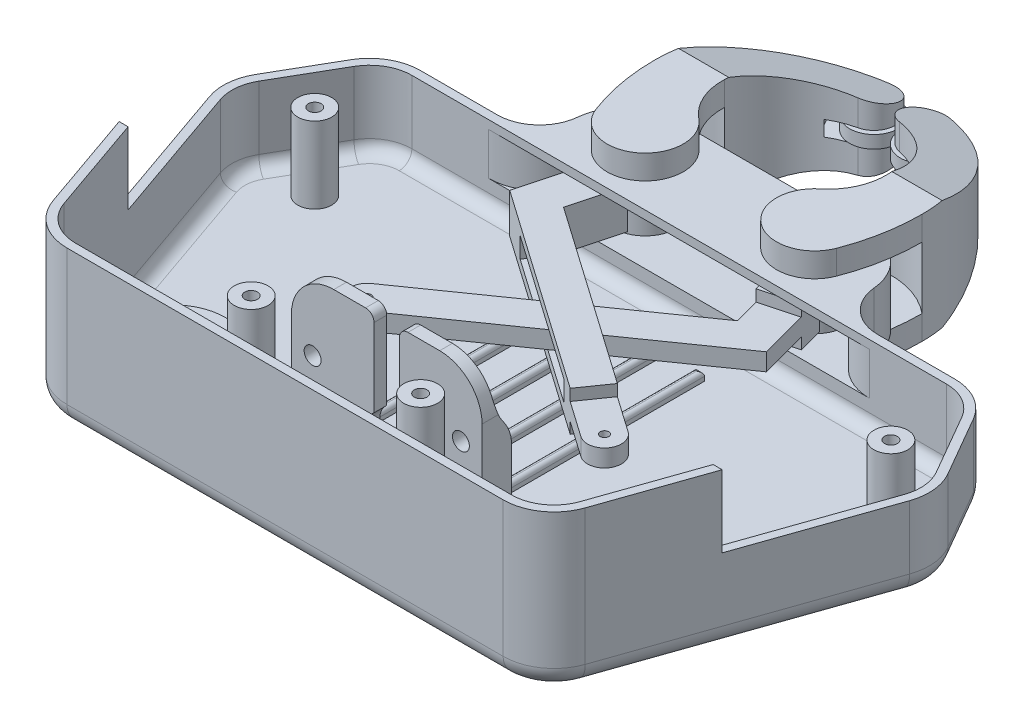
SolidWorks part; units mm, degrees
ref_plane "Front Plane" through (0, 0, 0) normal (0, 0, 1) x (1, 0, 0)
ref_plane "Top Plane" through (0, 0, 0) normal (0, 1, 0) x (1, 0, 0)
ref_plane "Right Plane" through (0, 0, 0) normal (1, 0, 0) x (0, 0, -1)
sketch "Sketch1" plane through (0, 0, 0) normal (0, 1, 0) x (1, 0, 0)
  line L0 (-70, -55) -> (-35, -55)
  line L1 (70, -55) -> (84.4338, -80)
  line L2 (84.4338, -80) -> (60, -150)
  line L3 (60, -150) -> (-60, -150)
  line L4 (-60, -150) -> (-84.4338, -80)
  line L5 (-84.4338, -80) -> (-70, -55)
  line L6 (-35, -55) -> (-35, -35)
  line L7 (-35, -35) -> (35, -35)
  line L8 (35, -35) -> (35, -55)
  line L9 (0, -55) -> (0, -122.8119) construction
  line L10 (35, -55) -> (70, -55)
  point P15 (0, -150)
  dimension "D1" = 25
  dimension "D2" = 140
  dimension "D3" = 70
  dimension "D4" = 120
  dimension "D5" = 70
  dimension "D6" = 55
  dimension "D7" = 120
  dimension "D8" = 20
  dimension "D9" = 70
  dimension "D10" = 35
extrude "Boss-Extrude1" add sketch "Sketch1" along normal blind 2
sketch "Sketch2" plane through (0, 2, 0) normal (0, 1, 0) x (1, 0, 0)
  line L0 (84.4338, -80) -> (70, -55) construction
  line L1 (60, -150) -> (84.4338, -80) construction
  line L2 (-60, -150) -> (60, -150) construction
  line L3 (-84.4338, -80) -> (-60, -150) construction
  line L4 (-70, -55) -> (-84.4338, -80) construction
  line L6 (84.4338, -80) -> (70, -55)
  line L7 (60, -150) -> (84.4338, -80)
  line L8 (-60, -150) -> (60, -150)
  line L9 (-84.4338, -80) -> (-60, -150)
  line L10 (-70, -55) -> (-84.4338, -80)
  line L11 (70, -55) -> (35, -55)
  line L12 (68.8453, -57) -> (33, -57)
  line L13 (-68.8453, -57) -> (-82.2434, -80.2062)
  line L14 (-82.2434, -80.2062) -> (-58.5798, -148)
  line L15 (-58.5798, -148) -> (58.5798, -148)
  line L16 (58.5798, -148) -> (82.2434, -80.2062)
  line L17 (82.2434, -80.2062) -> (68.8453, -57)
  line L18 (-35, -55) -> (-35, -35)
  line L19 (-35, -35) -> (35, -35)
  line L20 (35, -35) -> (35, -55)
  line L21 (-35, -55) -> (-70, -55)
  line L22 (-33, -57) -> (-33, -37)
  line L23 (70, -55) -> (-70, -55) construction
  line L24 (-33, -37) -> (33, -37)
  line L25 (33, -37) -> (33, -57)
  line L26 (-33, -57) -> (-68.8453, -57)
  line L28 (68.8453, -57) -> (-68.8453, -57) construction
  dimension "D1" = 2
  dimension "D2" = 2
  dimension "D3" = 2
  dimension "D4" = 2
extrude "Boss-Extrude2" add sketch "Sketch2" along normal blind 35
sketch "Sketch20" plane through (0, 0, 0) normal (0, -1, 0) x (1, 0, 0)
  line L0 (70, 55) -> (35, 55) construction
  line L1 (-35, 35) -> (35, 35)
  line L2 (-35, 35) -> (-35, 55)
  line L3 (-35, 55) -> (35, 55)
  line L4 (35, 35) -> (35, 55)
  line L5 (35, 55) -> (35, 35) construction
  line L6 (35, 35) -> (-35, 35) construction
  line L7 (-35, 35) -> (-35, 55) construction
extrude "Cut-Extrude7" cut sketch "Sketch20" against normal blind 8
sketch "Sketch21" plane through (0, 8, 0) normal (0, -1, 0) x (1, 0, 0)
  line L1 (-35, 35) -> (35, 35)
  line L2 (-35, 35) -> (-35, 55)
  line L3 (-35, 55) -> (35, 55)
  line L4 (35, 35) -> (35, 55)
extrude "Boss-Extrude12" add sketch "Sketch21" along normal blind 2
sketch "Sketch22" plane through (0, 0, 55) normal (0, 0, 1) x (1, 0, 0)
  line L1 (-33, 2) -> (33, 2)
  line L2 (-33, 2) -> (-33, 8)
  line L3 (-33, 8) -> (33, 8)
  line L4 (33, 2) -> (33, 8)
extrude "Boss-Extrude13" add sketch "Sketch22" along normal blind 2
sketch "Sketch23" plane through (0, 37, 0) normal (0, 1, 0) x (1, 0, 0)
  line L0 (35, -35) -> (-35, -35) construction
  line L1 (-35, -57) -> (35, -57)
  line L2 (-35, -57) -> (-35, -35)
  line L3 (-35, -35) -> (35, -35)
  line L4 (35, -57) -> (35, -35)
  line L5 (-35, -35) -> (-35, -55) construction
  line L6 (35, -55) -> (35, -35) construction
  line L7 (33, -57) -> (-33, -57) construction
extrude "Cut-Extrude8" cut sketch "Sketch23" against normal offset from surface (19 mm away) 12 up to face at (0, 6, 45)
sketch "Sketch24" plane through (0, 18, 0) normal (0, 1, 0) x (1, 0, 0)
  line L1 (-35, -35) -> (35, -35)
  line L2 (-35, -35) -> (-35, -57)
  line L3 (-35, -57) -> (35, -57)
  line L4 (35, -35) -> (35, -57)
  line L5 (-35, -35) -> (35, -35) construction
  line L6 (-35, -55) -> (-35, -35) construction
  line L8 (35, -35) -> (35, -55) construction
  line L9 (-35, -57) -> (-68.8453, -57) construction
extrude "Boss-Extrude16" add sketch "Sketch24" along normal blind 2
sketch "Sketch26" plane through (0, 0, 0) normal (0, -1, 0) x (1, 0, 0)
  line L0 (0, 35) -> (0, 168.1743) construction
  line L1 (-35, 35) -> (35, 35) construction
  circle A0 centre (20, 45) radius 7.5
  circle A1 centre (-20, 45) radius 7.5
  dimension "D1" = 15
  dimension "D2" = 10
  dimension "D3" = 20
extrude "Cut-Extrude9" cut sketch "Sketch26" against normal through all
sketch "Sketch27" plane through (0, 8, 0) normal (0, 1, 0) x (1, 0, 0)
  line L0 (-29.5, -45) -> (-27.5, -45)
  line L1 (-10.5, -45) -> (-12.5, -45)
  line L2 (0, -35) -> (0, -72.4721) construction
  line L3 (35, -35) -> (-35, -35) construction
  line L4 (29.5, -45) -> (27.5, -45)
  line L5 (10.5, -45) -> (12.5, -45)
  arc A0 (-27.5, -45) -> (-12.5, -45) centre (-20, -45) cw
  circle A1 centre (-20, -45) radius 7.5 construction
  arc A2 (-10.5, -45) -> (-29.5, -45) centre (-20, -45) ccw
  arc A3 (27.5, -45) -> (12.5, -45) centre (20, -45) ccw
  arc A4 (10.5, -45) -> (29.5, -45) centre (20, -45) cw
  dimension "D1" = 9.5
extrude "Boss-Extrude18" add sketch "Sketch27" along normal up to surface (10 mm away) up to face at (20, 18, 52.5)
sketch "Sketch25" plane through (0, 20, 0) normal (0, 1, 0) x (1, 0, 0)
  line L0 (35, -57) -> (35, -55) construction
  line L1 (-35, -57) -> (35, -57)
  line L2 (-35, -57) -> (-35, -55)
  line L3 (-35, -55) -> (35, -55)
  line L4 (35, -57) -> (35, -55)
  line L5 (-35, -57) -> (35, -57) construction
  line L6 (-35, -55) -> (-35, -57) construction
  line L7 (-35, -55) -> (-70, -55) construction
extrude "Boss-Extrude17" add sketch "Sketch25" along normal up to surface (17 mm away) up to face at (0, 37, 85.2758)
fillet "Fillet8" radius 10 2 edges at (-33, 13, 37) (33, 13, 37)
fillet "Fillet9" radius 12 2 edges at (35, 13, 35) (-35, 13, 35)
sketch "Sketch32" plane through (0, 6, 0) normal (0, -1, 0) x (1, 0, 0)
  circle A0 centre (-20, 45) radius 7.35
  circle A1 centre (-20, 45) radius 7.5 construction
  dimension "D1" = 14.7
extrude "Boss-Extrude22" add sketch "Sketch32" against normal offset from surface (14.6 mm away) 0.3 from offset 0.3 separate body up to face at (0, 20, 44.8382) offset beyond the face yes
ref_plane "Plane6" through (0, 13, 0) normal (0, -1, 0) x (-1, 0, 0)
sketch "Sketch34" plane through (0, 13, 0) normal (0, -1, 0) x (-1, 0, 0)
  line L0 (0, -55) -> (0, -6.1056) construction
  line L1 (-35, -55) -> (35, -55) construction
  circle A0 centre (6, -5) radius 6
  circle A1 centre (20, -45) radius 7.5 construction
  circle A2 centre (20, -45) radius 7.5 construction
  circle A3 centre (6, -5) radius 2.8
  dimension "D1" = 12
  dimension "D3" = 5.6
  dimension "D2" = 40
extrude "Boss-Extrude23" add sketch "Sketch34" along normal mid plane 3 separate body
sketch "Sketch36" plane through (0, 13, 0) normal (0, -1, 0) x (-1, 0, 0)
  circle A0 centre (6, -5) radius 2.5
  dimension "D1" = 5
extrude "Boss-Extrude24" add sketch "Sketch36" along normal mid plane 3.6 separate body
sketch "Sketch37" plane through (0, 11.2, 0) normal (0, -1, 0) x (1, 0, 0)
  line L0 (-1.0405, 27.7489) -> (-20, 45) construction
  line L1 (-6, 5) -> (-1.0405, 27.7489) construction
  line L2 (0.4875, 31.2396) -> (-20, 45) construction
  line L3 (0.4875, 31.2396) -> (-6, 5) construction
  arc A0 (-4.935, 9.8853) -> (-7.2001, 0.1462) centre (-6, 5) cw
  circle A1 centre (-20, 45) radius 7.35 construction
  arc A2 (-14.5636, 40.0535) -> (-26.1015, 49.0981) centre (-20, 45) ccw construction
  arc A3 (-4.935, 9.8853) -> (-14.5636, 40.0535) centre (-1.0405, 27.7489) cw construction
  arc A4 (-26.1015, 49.0981) -> (-7.2001, 0.1462) centre (0.4875, 31.2396) ccw construction
  arc A5 (-31.5421, 31.1877) -> (-19.3089, 27.0133) centre (-20, 45) ccw
  arc A6 (-31.5421, 31.1877) -> (-7.2001, 0.1462) centre (0.4875, 31.2396) ccw
  arc A7 (-19.3089, 27.0133) -> (-4.935, 9.8853) centre (-1.0405, 27.7489) ccw
  dimension "D1" = 5
  dimension "D4" = 18
  dimension "D2" = 60
  dimension "D3" = 70
extrude "Boss-Extrude25" add sketch "Sketch37" along normal up to surface (11.2 mm away) up to face at (0, 0, 95)
sketch "Sketch39" plane through (0, 5.7, 0) normal (0, -1, 0) x (1, 0, 0)
  arc A0 (-14.3353, 38.0064) -> (-28.4038, 48.2211) centre (-20, 45) ccw
  arc A1 (-31.5421, 31.1877) -> (-19.3089, 27.0133) centre (-20, 45) ccw construction
  arc A2 (-31.5421, 31.1877) -> (-19.3089, 27.0133) centre (-20, 45) ccw
  arc A3 (-31.5421, 31.1877) -> (-28.4038, 48.2211) centre (15.8356, 31.2644) cw
  arc A4 (-31.5421, 31.1877) -> (-7.2001, 0.1462) centre (0.4875, 31.2396) ccw construction
  arc A5 (-19.3089, 27.0133) -> (-14.3353, 38.0064) centre (-5.8694, 27.5545) cw
  arc A6 (-19.3089, 27.0133) -> (-4.935, 9.8853) centre (-1.0405, 27.7489) ccw construction
  dimension "D1" = 18
extrude "Boss-Extrude26" add sketch "Sketch39" along direction (0, -1, 0) on the side of the normal up to surface (5.7 mm away) up to face at (-16.6764, 0, 14.8256)
sketch "Sketch40" plane through (0, 20.3, 0) normal (0, 1, 0) x (1, 0, 0)
  arc A1 (-28.4038, -48.2211) -> (-14.3353, -38.0064) centre (-20, -45) ccw construction
  arc A2 (-19.3089, -27.0133) -> (-14.3353, -38.0064) centre (-5.8694, -27.5545) ccw construction
  arc A3 (-19.3089, -27.0133) -> (-31.5421, -31.1877) centre (-20, -45) ccw construction
  arc A4 (-31.5421, -31.1877) -> (-28.4038, -48.2211) centre (15.8356, -31.2644) ccw construction
  arc A5 (-28.4038, -48.2211) -> (-14.3353, -38.0064) centre (-20, -45) ccw
  arc A6 (-19.3089, -27.0133) -> (-14.3353, -38.0064) centre (-5.8694, -27.5545) ccw
  arc A7 (-19.3089, -27.0133) -> (-31.5421, -31.1877) centre (-20, -45) ccw
  arc A8 (-31.5421, -31.1877) -> (-28.4038, -48.2211) centre (15.8356, -31.2644) ccw
extrude "Boss-Extrude27" add sketch "Sketch40" along normal blind 5.7
sketch "Sketch41" plane through (0, 14.8, 0) normal (0, 1, 0) x (1, 0, 0)
  arc A0 (-4.935, -9.8853) -> (-7.2001, -0.1462) centre (-6, -5) ccw construction
  arc A1 (-19.3089, -27.0133) -> (-31.5421, -31.1877) centre (-20, -45) ccw construction
  arc A2 (-4.935, -9.8853) -> (-19.3089, -27.0133) centre (-1.0405, -27.7489) ccw construction
  arc A3 (-7.2001, -0.1462) -> (-31.5421, -31.1877) centre (0.4875, -31.2396) ccw construction
  arc A4 (-4.935, -9.8853) -> (-7.2001, -0.1462) centre (-6, -5) ccw
  arc A5 (-19.3089, -27.0133) -> (-31.5421, -31.1877) centre (-20, -45) ccw
  arc A6 (-4.935, -9.8853) -> (-19.3089, -27.0133) centre (-1.0405, -27.7489) ccw
  arc A7 (-7.2001, -0.1462) -> (-31.5421, -31.1877) centre (0.4875, -31.2396) ccw
extrude "Boss-Extrude28" add sketch "Sketch41" along normal up to surface (11.2 mm away) up to face at (-22.3518, 26, 38.2988)
sketch "Sketch43" plane through (0, 11.2, 0) normal (0, 1, 0) x (1, 0, 0)
  arc A1 (-4.935, -9.8853) -> (-19.3089, -27.0133) centre (-1.0405, -27.7489) ccw construction
  arc A3 (-19.3089, -27.0133) -> (-31.5421, -31.1877) centre (-20, -45) ccw construction
  arc A5 (-10.5871, -12.156) -> (-19.3089, -27.0133) centre (-1.0405, -27.7489) ccw
  arc A6 (-7.2001, -0.1462) -> (-31.5421, -31.1877) centre (0.4875, -31.2396) ccw construction
  arc A7 (-19.3089, -27.0133) -> (-31.5421, -31.1877) centre (-20, -45) ccw
  arc A8 (-14.2045, -2.7783) -> (-10.5871, -12.156) centre (-6, -5) ccw
  arc A9 (-14.2045, -2.7783) -> (-31.5421, -31.1877) centre (0.4875, -31.2396) ccw
  arc A13 (-4.935, -9.8853) -> (-7.2001, -0.1462) centre (-6, -5) ccw construction
  dimension "D1" = 17
extrude "Boss-Extrude29" add sketch "Sketch43" along normal up to surface (3.6 mm away) up to face at (-6, 14.8, 2.5)
sketch "Sketch44" plane through (0, 0, 0) normal (1, 0, 0) x (0, 0, -1)
  line L0 (0, 17.8) -> (-26.0133, 26)
  line L1 (-26.0133, 26) -> (0, 26)
  line L4 (0, 14.8) -> (0, 26) construction
  line L5 (-9.8853, 26) -> (-27.0133, 26) construction
  line L6 (0, 17.8) -> (0, 26)
  line L7 (-15.422, 13) -> (22.0298, 13) construction
  line L8 (-94.4278, 13) -> (94.4278, 13) construction
  line L9 (0, 8.2) -> (-26.0133, 0)
  line L10 (-26.0133, 0) -> (0, 0)
  line L11 (0, 8.2) -> (0, 0)
  dimension "D1" = 1
  dimension "D2" = 3
extrude "Cut-Extrude10" cut sketch "Sketch44" against normal up to surface (31.1129 mm away) up to face at (-19.4224, 13, 12.2098)
ref_plane "Plane2" through (0, 0, 0) normal (1, 0, 0) x (0, 0, -1)
ref_plane "Plane3" through (0, 0, 126) normal (0, 0, -1) x (-1, 0, 0)
sketch "Sketch45" plane through (0, 13, 0) normal (0, -1, 0) x (-1, 0, 0)
  circle A0 centre (6, -5) radius 6 construction
  circle A1 centre (6, -5) radius 6
  circle A2 centre (6, -5) radius 5.75
  dimension "D1" = 11.5
extrude "Cut-Extrude11" cut sketch "Sketch45" along normal up to surface (1.5 mm away) from surface up to face at (-6, 11.5, -1) starting at face at (-6, 14.5, -1)
mirror "Mirror8" about plane through (0, 0, 0) normal (1, 0, 0) of bodies 137 140
sketch "Sketch8" plane through (0, 0, 126) normal (0, 0, -1) x (-1, 0, 0)
  line L0 (-68.8453, 2) -> (68.8453, 2) construction
  line L1 (-68.8453, 2) -> (68.8453, 2) construction
  line L2 (60, 0) -> (-60, 0) construction
  line L3 (22.5, 2) -> (-22.5, 2)
  line L4 (22.5, 2) -> (22.5, 36)
  line L5 (22.5, 36) -> (-22.5, 36)
  line L6 (-22.5, 2) -> (-22.5, 36)
  line L7 (60, 0) -> (-60, 0) construction
  line L8 (0, 14.8493) -> (0, -14.8493) construction
  dimension "D1" = 34
  dimension "D2" = 45
  dimension "D3" = 22.5
extrude "Boss-Extrude5" add sketch "Sketch8" along normal blind 3
sketch "Sketch9" plane through (0, 2, 0) normal (0, 1, 0) x (1, 0, 0)
  line L1 (-22.5, -123) -> (-19.5, -123)
  line L2 (-22.5, -123) -> (-22.5, -119)
  line L3 (-22.5, -119) -> (-19.5, -119)
  line L4 (-19.5, -123) -> (-19.5, -119)
  line L5 (22.5, -123) -> (19.5, -123)
  line L6 (22.5, -123) -> (22.5, -119)
  line L7 (22.5, -119) -> (19.5, -119)
  line L8 (19.5, -123) -> (19.5, -119)
  dimension "D1" = 3
  dimension "D2" = 4
extrude "Boss-Extrude6" add sketch "Sketch9" along normal blind 20
fillet "Fillet1" radius 10 2 edges at (-21, 22, 123) (21, 22, 123)
fillet "Fillet2" radius 10 2 edges at (-21, 22, 119) (21, 22, 119)
sketch "Sketch11" plane through (0, 2, 0) normal (0, 1, 0) x (1, 0, 0)
  line L0 (-58.5798, -148) -> (58.5798, -148) construction
  circle A0 centre (-43.5798, -133) radius 12.5
  dimension "D1" = 25
  dimension "D2" = 15
  dimension "D3" = 15
extrude "Boss-Extrude9" add sketch "Sketch11" along normal blind 10
ref_plane "Plane4" through (0, 7, 0) normal (0, 1, 0) x (1, 0, 0)
sketch "Sketch13" plane through (0, 7, 0) normal (0, 1, 0) x (1, 0, 0)
  line L0 (-53.0211, -136.2955) -> (-58.294, -121.1894)
  line L1 (-82.2434, -80.2062) -> (-58.5798, -148) construction
  line L2 (-34.1384, -129.7045) -> (-39.4113, -114.5983)
  line L3 (-58.294, -121.1894) -> (-39.4113, -114.5983)
  arc A0 (-53.0211, -136.2955) -> (-34.1384, -129.7045) centre (-43.5798, -133) ccw
  dimension "D1" = 20
  dimension "D2" = 16
extrude "Cut-Extrude3" cut sketch "Sketch13" along normal blind 5 from offset 3 offset against normal yes
sketch "Sketch14" plane through (0, 12, 0) normal (0, 1, 0) x (1, 0, 0)
  circle A0 centre (-43.5798, -133) radius 2.5
  circle A1 centre (-43.5798, -133) radius 12.5 construction
  dimension "D1" = 5
extrude "Cut-Extrude4" cut sketch "Sketch14" against normal up to surface (8 mm away) up to face at (-44.4037, 4, 130.6397)
sketch "Sketch15" plane through (0, 0, 126) normal (0, 0, 1) x (1, 0, 0)
  line L1 (22.5, 2) -> (-22.5, 2) construction
  line L2 (22.5, 2) -> (-22.5, 2) construction
  line L3 (0, -14.8493) -> (0, 14.8493) construction
  circle A0 centre (17.5, 20) radius 2
  circle A1 centre (-17.5, 20) radius 2
  circle A3 centre (0, 12) radius 4.65
  dimension "D1" = 8
  dimension "D2" = 4
  dimension "D3" = 4
  dimension "D6" = 9.3
  dimension "D4" = 35
  dimension "D5" = 17.5
  dimension "D7" = 10
extrude "Cut-Extrude5" cut sketch "Sketch15" against normal up to surface (3 mm away) up to face at (0, 24.5, 123)
fillet "Fillet3" radius 10 8 edges at (-35, 13, 55) (35, 13, 55) (58.5798, 19.5, 148) (-58.5798, 19.5, 148) (82.2434, 19.5, 80.2062) (68.8453, 19.5, 57) (-82.2434, 19.5, 80.2062) (-68.8453, 19.5, 57)
fillet "Fillet4" radius 12 8 edges at (-60, 18.5, 150) (-84.4338, 18.5, 80) (-70, 18.5, 55) (-33, 13, 57) (33, 13, 57) (70, 18.5, 55) (60, 18.5, 150) (84.4338, 18.5, 80)
fillet "Fillet5" radius 10 2 edges at (22.5, 36, 124.5) (-22.5, 36, 124.5)
fillet "Fillet6" radius 3 12 edges at (-70.8266, 2, 112.9143) (-81.2478, 2, 80.3) (-75.842, 2, 69.1187) (-68.0718, 2, 58.3397) (0, 2, 57) (68.0718, 2, 58.3397) (75.842, 2, 69.1187) (81.2478, 2, 80.3) (70.8266, 2, 112.9143) (0, 2, 148) (-57.2685, 2, 146.1534) (57.2685, 2, 146.1534)
fillet "Fillet7" radius 5 12 edges at (69.0718, 0, 56.6077) (77.5741, 0, 68.1187) (83.2389, 0, 80.1125) (72.7148, 0, 113.5734) (58.4264, 0, 147.7841) (0, 0, 150) (-58.4264, 0, 147.7841) (-72.7148, 0, 113.5734) (-83.2389, 0, 80.1125) (-77.5741, 0, 68.1187) (-69.0718, 0, 56.6077) (0, 0, 55)
sketch "Sketch16" plane through (0, 0, 0) normal (1, 0, 0) x (0, 0, -1)
  line L0 (-83.5443, 0) -> (-140.3069, 0) construction
  line L1 (-118, 40) -> (-28, 40)
  line L2 (-118, 40) -> (-118, 20)
  line L3 (-118, 20) -> (-28, 20)
  line L4 (-28, 40) -> (-28, 20)
  line L5 (-150, 5) -> (-150, 37) construction
  dimension "D1" = 20
  dimension "D2" = 32
  dimension "D3" = 20
  dimension "D4" = 90
extrude "Cut-Extrude6" cut sketch "Sketch16" against normal through all both and the other way through all
sketch "Sketch17" plane through (0, 2, 0) normal (0, 1, 0) x (1, 0, 0)
  line L0 (0, -14.8493) -> (0, 14.8493) construction
  line L4 (-63.0718, -55) -> (-44.9089, -55) construction
  circle A2 centre (-68, -75) radius 4
  circle A4 centre (-68, -75) radius 1.5
  circle A10 centre (68, -75) radius 1.5
  circle A11 centre (68, -75) radius 4
  dimension "D7" = 8
  dimension "D9" = 3
  dimension "D4" = 20
  dimension "D5" = 68
extrude "Boss-Extrude10" add sketch "Sketch17" along normal up to surface (18 mm away) up to face at (0, 20, 71.1525)
sketch "Sketch19" plane through (0, 2, 0) normal (0, 1, 0) x (1, 0, 0)
  line L0 (0, -14.8493) -> (0, 14.8493) construction
  line L1 (-51.4786, -150) -> (51.4786, -150) construction
  circle A0 centre (-20, -138) radius 4
  circle A1 centre (-20, -138) radius 1.5
  circle A2 centre (20, -138) radius 1.5
  circle A3 centre (20, -138) radius 4
  dimension "D1" = 3
  dimension "D2" = 8
  dimension "D3" = 20
  dimension "D4" = 12
extrude "Boss-Extrude11" add sketch "Sketch19" along normal up to surface (35 mm away) up to face at (0, 37, 136.7604)
sketch "Sketch46" plane through (0, 0, 126) normal (0, 0, 1) x (1, 0, 0)
  line L0 (-3, 12) -> (-3, 36)
  line L1 (-3, 36) -> (3, 36)
  line L3 (-3, 12) -> (3, 12)
  line L5 (-12.5, 36) -> (12.5, 36) construction
  line L7 (3, 36) -> (3, 12)
  circle A0 centre (0, 12) radius 4.65 construction
  circle A1 centre (0, 12) radius 4.65 construction
  dimension "D1" = 6
extrude "Cut-Extrude12" cut sketch "Sketch46" against normal up to surface (3 mm away) up to face at (-4.65, 12, 123)
fillet "Fillet10" radius 2 2 edges at (-3, 36, 124.5) (3, 36, 124.5)
mirror "Mirror9" about plane through (0, 0, 0) normal (1, 0, 0) of "Cut-Extrude4", "Cut-Extrude3", "Boss-Extrude9"
sketch "Sketch49" plane through (0, 13, 0) normal (0, -1, 0) x (-1, 0, 0)
  line L0 (20, -45) -> (6, -5) construction
  line L1 (27.0996, -43.0977) -> (32.923, -64.831) construction
  line L2 (30.3078, -66.6622) -> (-25.7197, -105.8931)
  line L3 (12.9004, -46.9023) -> (17.9052, -65.5804) construction
  line L4 (17.9052, -65.5804) -> (-30.3083, -99.3398)
  line L5 (63.0718, -57) -> (-63.0718, -57) construction
  line L6 (30.3078, -66.6622) -> (25.7352, -49.5968)
  line L7 (20.5204, -63.7492) -> (17.3316, -51.8485)
  line L8 (17.9052, -65.5804) -> (20.5204, -63.7492)
  line L9 (30.3078, -66.6622) -> (32.923, -64.831) construction
  circle A0 centre (20, -45) radius 7.35 construction
  arc A1 (17.3316, -51.8485) -> (25.7352, -49.5968) centre (20, -45) ccw
  circle A2 centre (20, -45) radius 75 construction
  arc A3 (7.2001, -0.1462) -> (4.935, -9.8853) centre (6, -5) ccw construction
  arc A4 (7.2001, -0.1462) -> (4.935, -9.8853) centre (6, -5) ccw construction
  arc A5 (-30.3083, -99.3398) -> (-25.7197, -105.8931) centre (-28.014, -102.6165) ccw
  point P15 (26.4546, -40.6906)
  point P19 (0, 0)
  point P20 (27.0996, -43.0977)
  dimension "D1" = 150
  dimension "D2" = 110
  dimension "D3" = 4
  dimension "D4" = 22.5
  dimension "D5" = 35
  dimension "D6" = 3
  dimension "D7" = 3
extrude "Boss-Extrude30" add sketch "Sketch49" along normal offset from surface 0.3 and the other way offset from surface 0.3 separate body up to face at (0, 8, 45.5486) other way up to face at (0, 18, 45.5486)
sketch "Sketch50" plane through (-41.2919, 0, 58.971) normal (-0.5736, 0, 0.8192) x (0.8192, 0, 0.5736)
  line L0 (13.4091, 8.3) -> (13.4091, 17.7) construction
  line L1 (23.4091, 15.4) -> (65.8061, 15.4)
  line L2 (23.4091, 15.4) -> (23.4091, 10.6)
  line L3 (23.4091, 10.6) -> (65.8061, 10.6)
  line L4 (65.8061, 15.4) -> (65.8061, 10.6)
  line L5 (85.8061, 8.3) -> (85.8061, 17.7) construction
  line L6 (23.4091, 15.4) -> (23.4091, 17.7) construction
  line L7 (81.8061, 17.7) -> (13.4091, 17.7) construction
  line L8 (23.4091, 10.6) -> (23.4091, 8.3) construction
  line L9 (13.4091, 8.3) -> (81.8061, 8.3) construction
  dimension "D1" = 4.8
  dimension "D2" = 10
  dimension "D3" = 20
extrude "Cut-Extrude13" cut sketch "Sketch50" against normal up to surface (8 mm away) up to face at (4.894, 13, 81.5445)
sketch "Sketch51" plane through (0, 13, 0) normal (0, -1, 0) x (-1, 0, 0)
  line L0 (30.3078, -66.6622) -> (25.7352, -49.5968) construction
  line L1 (17.3316, -51.8485) -> (20.5204, -63.7492) construction
  line L3 (-25.7197, -105.8931) -> (30.3078, -66.6622) construction
  line L6 (20.5204, -63.7492) -> (-30.3083, -99.3398) construction
  line L22 (17.3316, -51.8485) -> (20.5204, -63.7492) construction
  line L23 (20.5204, -63.7492) -> (-30.3083, -99.3398) construction
  line L24 (-25.7197, -105.8931) -> (30.3078, -66.6622) construction
  line L25 (30.3078, -66.6622) -> (25.7352, -49.5968) construction
  line L26 (0, 14.8493) -> (0, -14.8493) construction
  line L27 (-20.5204, -63.7492) -> (30.3083, -99.3398)
  line L28 (-17.3316, -51.8485) -> (-20.5204, -63.7492)
  line L29 (-30.3078, -66.6622) -> (-25.7352, -49.5968)
  line L30 (25.7197, -105.8931) -> (-30.3078, -66.6622)
  arc A0 (17.3316, -51.8485) -> (25.7352, -49.5968) centre (20, -45) ccw construction
  arc A6 (-30.3083, -99.3398) -> (-25.7197, -105.8931) centre (-28.014, -102.6165) ccw construction
  arc A10 (-30.3083, -99.3398) -> (-25.7197, -105.8931) centre (-28.014, -102.6165) ccw construction
  arc A11 (17.3316, -51.8485) -> (25.7352, -49.5968) centre (20, -45) ccw construction
  arc A12 (30.3083, -99.3398) -> (25.7197, -105.8931) centre (28.014, -102.6165) cw
  arc A13 (-17.3316, -51.8485) -> (-25.7352, -49.5968) centre (-20, -45) cw
extrude "Boss-Extrude32" add sketch "Sketch51" along normal offset from surface 0.3 and the other way offset from surface 0.4 up to face at (-2.4572, 10.6, 81.2803) other way up to face at (-2.4572, 15.4, 81.2803)
sketch "Sketch52" plane through (0, 13, 0) normal (0, -1, 0) x (-1, 0, 0)
  line L2 (-25.7352, -49.5968) -> (-30.3078, -66.6622) construction
  line L3 (-20.5204, -63.7492) -> (-17.3316, -51.8485) construction
  line L6 (-25.7352, -49.5968) -> (-27.3076, -55.4652)
  line L7 (-18.9041, -57.717) -> (-17.3316, -51.8485)
  line L9 (-18.9041, -57.717) -> (-27.3076, -55.4652)
  line L10 (63.0718, -57) -> (-63.0718, -57) construction
  arc A0 (-25.7352, -49.5968) -> (-17.3316, -51.8485) centre (-20, -45) ccw construction
  arc A1 (-25.7352, -49.5968) -> (-17.3316, -51.8485) centre (-20, -45) ccw
  circle A2 centre (-20, -45) radius 12 construction
  point P2 (-27.4936, -56.1593)
extrude "Boss-Extrude33" add sketch "Sketch52" along normal up to surface (4.7 mm away) from surface up to face at (-5.8265, 8.3, 73.4601) starting at face at (-5.8265, 17.7, 73.4601)
sketch "Sketch53" plane through (0, 17.7, 0) normal (0, 1, 0) x (1, 0, 0)
  line L0 (-20.5204, -63.7492) -> (30.3083, -99.3398) construction
  line L1 (25.7197, -105.8931) -> (-30.3078, -66.6622) construction
  line L2 (21.8792, -93.4377) -> (30.3083, -99.3398)
  line L3 (25.7197, -105.8931) -> (17.2906, -99.9909)
  line L4 (17.2906, -99.9909) -> (21.8792, -93.4377)
  arc A0 (25.7197, -105.8931) -> (30.3083, -99.3398) centre (28.014, -102.6165) ccw construction
  arc A1 (25.7197, -105.8931) -> (30.3083, -99.3398) centre (28.014, -102.6165) ccw
  point P5 (31.2906, -104.9108)
  dimension "D1" = 14
extrude "Cut-Extrude14" cut sketch "Sketch53" against normal up to surface (2.7 mm away) up to face at (6.2892, 15, 75.1868)
sketch "Sketch54" plane through (0, 8.3, 0) normal (0, -1, 0) x (1, 0, 0)
  line L0 (25.7197, 105.8931) -> (17.2906, 99.9909) construction
  line L1 (21.8792, 93.4377) -> (30.3083, 99.3398) construction
  line L2 (17.2906, 99.9909) -> (21.8792, 93.4377) construction
  line L3 (25.7197, 105.8931) -> (17.2906, 99.9909)
  line L4 (21.8792, 93.4377) -> (30.3083, 99.3398)
  line L5 (17.2906, 99.9909) -> (21.8792, 93.4377)
  arc A0 (30.3083, 99.3398) -> (25.7197, 105.8931) centre (28.014, 102.6165) ccw construction
  arc A1 (30.3083, 99.3398) -> (25.7197, 105.8931) centre (28.014, 102.6165) ccw
extrude "Cut-Extrude15" cut sketch "Sketch54" against normal up to surface (2.6 mm away) up to face at (6.2892, 10.9, 75.1868)
sketch "Sketch55" plane through (0, 15, 0) normal (0, 1, 0) x (1, 0, 0)
  arc A0 (-30.3083, -99.3398) -> (-25.7197, -105.8931) centre (-28.014, -102.6165) ccw construction
  arc A1 (25.7197, -105.8931) -> (30.3083, -99.3398) centre (28.014, -102.6165) ccw construction
  arc A2 (-30.3083, -99.3398) -> (-25.7197, -105.8931) centre (-28.014, -102.6165) ccw construction
  arc A3 (25.7197, -105.8931) -> (30.3083, -99.3398) centre (28.014, -102.6165) ccw construction
  circle A4 centre (-28.014, -102.6165) radius 1
  circle A5 centre (28.014, -102.6165) radius 1
  dimension "D1" = 2
  dimension "D2" = 2
extrude "Cut-Extrude16" cut sketch "Sketch55" against normal up to surface (4.1 mm away) up to face at (6.2892, 10.9, 75.1868)
sketch "Sketch56" plane through (0, 2, 0) normal (0, 1, 0) x (1, 0, 0)
  line L0 (0, -14.8493) -> (0, 14.8493) construction
  line L1 (-16, -119) -> (-14, -119)
  line L2 (-16, -119) -> (-16, -67)
  line L3 (-16, -67) -> (-14, -67)
  line L4 (-14, -119) -> (-14, -67)
  line L5 (-6, -119) -> (-4, -119)
  line L6 (-6, -119) -> (-6, -67)
  line L7 (-6, -67) -> (-4, -67)
  line L8 (-4, -119) -> (-4, -67)
  line L9 (-63.0718, -57) -> (63.0718, -57) construction
  point P10 (-7.2699, -121.6995)
  point P11 (0, 0)
  point P12 (0, 0)
  point P16 (0, 0)
  dimension "D1" = 4
  dimension "D2" = 8
  dimension "D3" = 10
  dimension "D4" = 2
extrude "Boss-Extrude34" add sketch "Sketch56" along normal blind 2
fillet "Fillet11" radius 1 8 edges at (-15, 4, 119) (-5, 4, 119) (-5, 4, 67) (-15, 4, 67) (-4, 4, 93) (-6, 4, 93) (-14, 4, 93) (-16, 4, 93)
mirror "Mirror11" about plane through (0, 0, 0) normal (1, 0, 0) of "Fillet11", "Boss-Extrude34"
